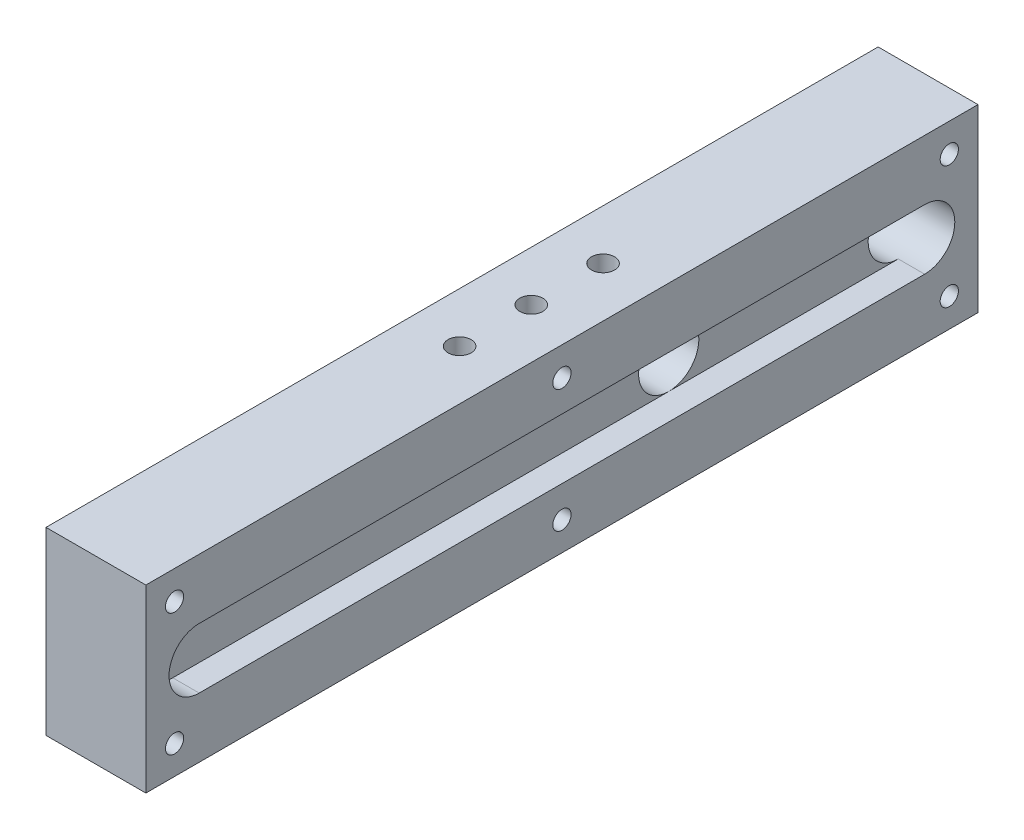
SolidWorks part; units mm, degrees
material "Delrin 2700 NC010, Low Viscosity Acetal Copolymer (SS)"
ref_plane "Front" through (0, 0, 0) normal (0, 0, 1) x (1, 0, 0)
ref_plane "Top" through (0, 0, 0) normal (0, 1, 0) x (1, 0, 0)
ref_plane "Right" through (0, 0, 0) normal (1, 0, 0) x (0, 0, -1)
sketch "Sketch1" plane through (0, 0, 0) normal (1, 0, 0) x (0, 0, -1)
  line L0 (-80.2752, 0) -> (80.2752, 0) construction
  line L1 (92.075, -19.939) -> (-92.075, -19.939)
  line L2 (92.075, -19.939) -> (92.075, 19.939)
  line L3 (92.075, 19.939) -> (-92.075, 19.939)
  line L4 (-92.075, -19.939) -> (-92.075, 19.939)
  line L5 (92.075, -19.939) -> (-92.075, 19.939) construction
  line L6 (92.075, 19.939) -> (-92.075, -19.939) construction
  line L7 (-80.2752, 6.6675) -> (80.2752, 6.6675)
  line L8 (-80.2752, -6.6675) -> (80.2752, -6.6675)
  arc A0 (-80.2752, 6.6675) -> (-80.2752, -6.6675) centre (-80.2752, 0) ccw
  arc A1 (80.2752, -6.6675) -> (80.2752, 6.6675) centre (80.2752, 0) ccw
  point P0 (0, 0)
  point P8 (0, 0)
  dimension "D4" = 13.335
  dimension "D1" = 160.5505
  dimension "D2" = 184.15
  dimension "D3" = 39.878
extrude "Boss-Extrude1" add sketch "Sketch1" along normal blind 22.098
hole_wizard "#10-32 Tapped Hole1" positions "Sketch3" profile "Sketch4" tap size "#10-32" standard "ANSI Inch" end condition through all
sketch "Sketch3" plane through (22.098, 0, 0) normal (1, 0, 0) x (0, 0, -1)
  line L0 (-85.725, 13.589) -> (0, 13.589) construction
  line L1 (0, 13.589) -> (85.725, 13.589) construction
  line L3 (-85.725, 19.939) -> (-85.725, 13.589) construction
  line L4 (92.075, 19.939) -> (-92.075, 19.939) construction
  line L5 (-85.725, 13.589) -> (-85.725, -13.589) construction
  line L6 (-85.725, -13.589) -> (-85.725, -19.939) construction
  line L7 (-92.075, -19.939) -> (92.075, -19.939) construction
  line L8 (-92.075, 19.939) -> (-92.075, -19.939) construction
  point P0 (-85.725, 13.589)
  point P2 (-85.725, -13.589)
  point P4 (0, -13.589)
  point P6 (85.725, -13.589)
  point P8 (85.725, 13.589)
  point P10 (0, 13.589)
  dimension "D1" = 6.35
  dimension "D2" = 6.35
sketch "Sketch4" plane through (22.098, 13.589, 85.725) normal (0, 1, 0) x (0, 0, -1)
  line L0 (0, 0) -> (0, 22.098)
  line L1 (0, 22.098) -> (2.0193, 22.098)
  line L2 (2.0193, 22.098) -> (2.0193, 0)
  line L5 (2.0193, 0) -> (0, 0)
  line L11 (0, -6.35) -> (0, 107.95) construction
  dimension "Thru Tap Drill Dia." = 4.0386
  dimension "Thru Tap Drill Depth" = 22.098
cosmetic thread "Hole Thread1" parameters "D2"=4.826
cosmetic thread "Hole Thread2" parameters "D2"=4.826
cosmetic thread "Hole Thread3" parameters "D2"=4.826
cosmetic thread "Hole Thread4" parameters "D2"=4.826
cosmetic thread "Hole Thread5" parameters "D2"=4.826
cosmetic thread "Hole Thread6" parameters "D2"=4.826
sketch "Sketch5" plane through (0, 0, 0) normal (-1, 0, 0) x (0, 0, 1)
  line L6 (-80.2752, -6.6675) -> (80.2752, -6.6675)
  line L7 (80.2752, 6.6675) -> (-80.2752, 6.6675)
  line L8 (-80.2752, -6.6675) -> (80.2752, -6.6675)
  line L9 (80.2752, 6.6675) -> (-80.2752, 6.6675)
  arc A1 (-80.2752, -6.6675) -> (-80.2752, 6.6675) centre (-80.2752, 0) ccw
  arc A7 (80.2752, -6.6675) -> (80.2752, 6.6675) centre (80.2752, 0) ccw
  arc A8 (-80.2752, 6.6675) -> (-80.2752, -6.6675) centre (-80.2752, 0) ccw
  arc A9 (80.2752, -6.6675) -> (80.2752, 6.6675) centre (80.2752, 0) ccw
  arc A11 (-80.2752, 6.6675) -> (-80.2752, -6.6675) centre (-80.2752, 0) ccw construction
  circle A12 centre (-29.4752, 0) radius 6.6675
  arc M15 (80.2752, 6.6675) -> (80.2752, -6.6675) centre (80.2752, 0) cw
  line M16 (80.2752, -6.6675) -> (-80.2752, -6.6675)
  line M18 (-80.2752, 6.6675) -> (80.2752, 6.6675)
  dimension "D2" = 50.8
  dimension "D1" = 0
extrude "Boss-Extrude2" add sketch "Sketch5" against normal offset from surface (16.256 mm away) 5.842 contours A12 A1 L8 M18 | A12 L9 M16 M15 region at (0, 0, -54.8752) region at (0, 0, 30.6366) up to face at (22.098, 13.589, 83.7057)
hole_wizard "1/4-20 Tapped Hole1" positions "Sketch6" profile "Sketch7" tap size "1/4-20" standard "ANSI Inch" end condition through all
sketch "Sketch6" plane through (0, 19.939, 0) normal (0, 1, 0) x (1, 0, 0)
  point P0 (11.049, -11.6043)
  point P6 (11.049, 20.1457)
  point P11 (11.049, 4.2707)
sketch "Sketch7" plane through (11.049, 19.939, 11.6043) normal (1, 0, 0) x (0, 0, 1)
  line L0 (0, 0) -> (0, 39.878)
  line L1 (0, 39.878) -> (2.5527, 39.878)
  line L2 (2.5527, 39.878) -> (2.5527, 0)
  line L5 (2.5527, 0) -> (0, 0)
  line L11 (0, -6.35) -> (0, 107.95) construction
  dimension "Thru Tap Drill Dia." = 5.1054
  dimension "Thru Tap Drill Depth" = 39.878
cosmetic thread "Hole Thread7" parameters "D2"=6.35
cosmetic thread "Hole Thread8" parameters "D2"=6.35
cosmetic thread "Hole Thread9" parameters "D2"=6.35
